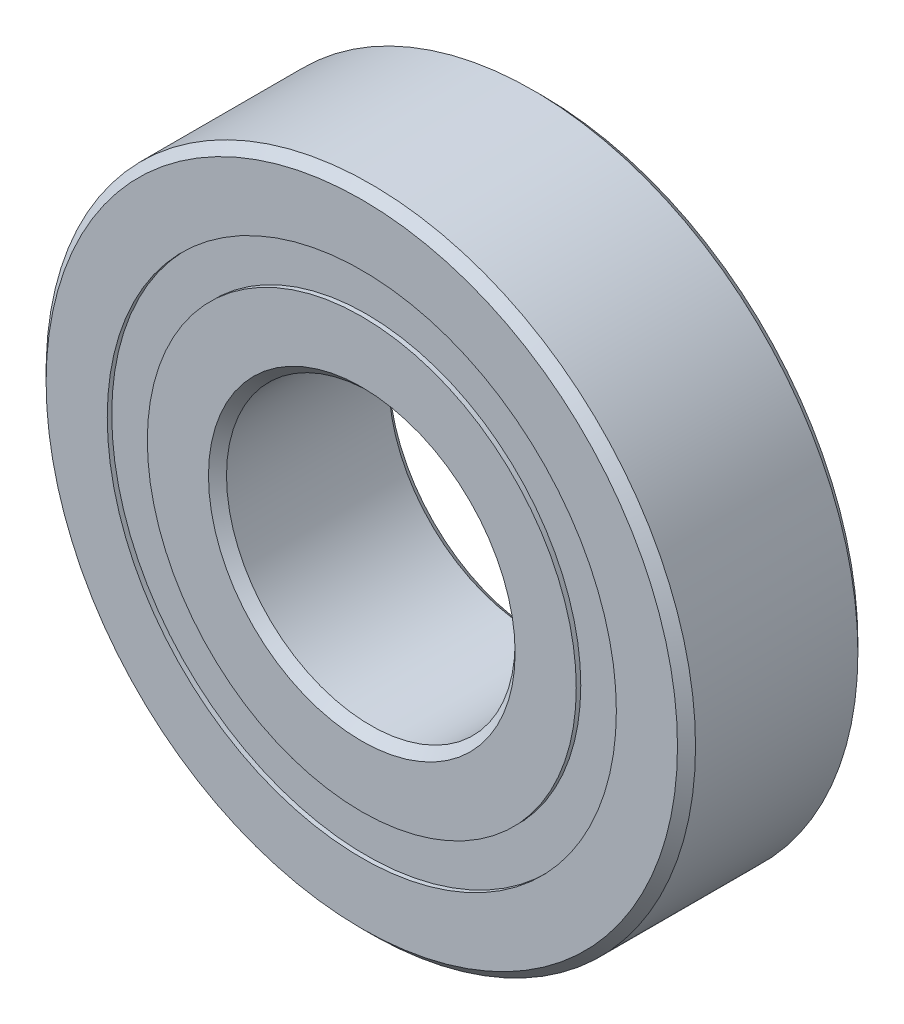
SolidWorks part; units mm, degrees
ref_plane "Front Plane" through (0, 0, 0) normal (0, 0, 1) x (1, 0, 0)
ref_plane "Top Plane" through (0, 0, 0) normal (0, 1, 0) x (1, 0, 0)
ref_plane "Right Plane" through (0, 0, 0) normal (1, 0, 0) x (0, 0, -1)
sketch "Sketch1" plane through (0, 0, 0) normal (1, 0, 0) x (0, 0, -1)
  line L0 (-1.25, 0) -> (1.25, 0) construction
  line L1 (0, 4.5) -> (0, -4.5) construction
  line L2 (1.125, 4.5) -> (-1.125, 4.5)
  line L3 (-1.125, 4.5) -> (-1.25, 4.375)
  line L4 (-1.25, 4.375) -> (-1.25, 3.5278)
  line L5 (-1.25, 3.5278) -> (-0.5556, 3.5278)
  line L6 (1.25, 3.5278) -> (0.5556, 3.5278)
  line L7 (1.25, 4.375) -> (1.25, 3.5278)
  line L8 (1.125, 4.5) -> (1.25, 4.375)
  line L9 (0, 4.5) -> (0, 3.25) construction
  line L10 (0, 3.25) -> (0, 2) construction
  arc A0 (-0.5556, 3.5278) -> (0.5556, 3.5278) centre (0, 3.25) cw
  arc A1 (-0.5556, 3.5278) -> (0.5556, 3.5278) centre (0, 3.25) ccw construction
  point P14 (0, 2)
  point P15 (0, -2)
  dimension "Width" = 2.5
  dimension "OD" = 9
  dimension "D1" = 45
  dimension "D2" = 0.125
  dimension "D3" = 1.1111
  dimension "Shaft Dia" = 4
  dimension "D4" = 0.2778
revolve "Revolve1" add sketch "Sketch1" angle 360 about L0
sketch "Sketch2" plane through (0, 0, 0) normal (1, 0, 0) x (0, 0, -1)
  line L0 (-1.25, 2.9722) -> (-0.5556, 2.9722)
  line L1 (-1.25, 4.375) -> (-1.25, -4.375) construction
  line L2 (-1.25, 2.9722) -> (-1.25, 2.125)
  line L3 (-1.25, 2.125) -> (-1.125, 2)
  line L4 (-1.125, 2) -> (1.125, 2)
  line L5 (0, 4.5) -> (0, -4.5) construction
  line L6 (0, 2) -> (0, 2.6289) construction
  line L7 (0, 2.6289) -> (0, 2) construction
  line L8 (-1.25, 2.9722) -> (-1.25, 1.2778) construction
  line L10 (1.25, 2.9722) -> (0.5556, 2.9722)
  line L11 (1.25, 2.9722) -> (1.25, 2.125)
  line L12 (1.25, 2.125) -> (1.125, 2)
  arc A0 (-0.5556, 2.9722) -> (0.5556, 2.9722) centre (0, 3.25) ccw
  arc A1 (0.5556, 3.5278) -> (-0.5556, 3.5278) centre (0, 3.25) ccw construction
  circle A2 centre (0, 3.25) radius 0.6211 construction
  dimension "D1" = 0.125
  dimension "D2" = 45
revolve "Revolve2" add sketch "Sketch2" angle 360 about L0
sketch "Sketch3" plane through (0, 0, 0) normal (1, 0, 0) x (0, 0, -1)
  line L0 (-0.6211, 3.25) -> (0.6211, 3.25)
  line L1 (0, 3.25) -> (0, 0) construction
  circle A1 centre (0, 3.25) radius 0.6211 construction
  arc A2 (-0.6211, 3.25) -> (0.6211, 3.25) centre (0, 3.25) cw
  arc A3 (0.5556, 3.5278) -> (-0.5556, 3.5278) centre (0, 3.25) ccw construction
  dimension "D1" = 1.2423
  dimension "D2" = 3.25
revolve "Revolve3" add sketch "Sketch3" angle 360 about L0
ref_axis "Axis1" through (0, 0, -1.25) along (0, 0, 1)
pattern_circular "CirPattern1" count 15 every 24 about axis through (0, 0, -1.25) along (0, 0, 1) of bodies 104
sketch "Sketch5" plane through (0, 0, 0) normal (1, 0, 0) x (0, 0, -1)
  line L0 (-1.25, 2.9722) -> (-0.5556, 2.9722) construction
  line L1 (-1.1875, 3.5278) -> (-0.6211, 3.5278)
  line L2 (-1.1875, 3.5278) -> (-1.1875, 2.9722)
  line L3 (-1.1875, 2.9722) -> (-0.6211, 2.9722)
  line L4 (-0.6211, 3.5278) -> (-0.6211, 2.9722)
  line L5 (0.6211, 3.5278) -> (1.1875, 3.5278)
  line L6 (0.6211, 3.5278) -> (0.6211, 2.9722)
  line L7 (0.6211, 2.9722) -> (1.1875, 2.9722)
  line L8 (1.1875, 3.5278) -> (1.1875, 2.9722)
  line L9 (-1.25, 3.5278) -> (-0.5556, 3.5278) construction
  line L10 (-1.1875, 4.4375) -> (-1.1875, 3.5278) construction
  line L11 (-1.125, 4.5) -> (-1.25, 4.375) construction
  circle A0 centre (0, 3.25) radius 0.6211 construction
revolve "Revolve5" add sketch "Sketch5" angle 360 about L0
sketch "Sketch6" plane through (0, 0, 0) normal (0, 1, 0) x (1, 0, 0)
  point P0 (4.5, -1.25)
  point P1 (4.5, 1.25)
  dimension "D1" = 2.5
ref_axis "Center Axis 1" through (0, 0, -2.2011) along (0, 0, 1)
ref_plane "Contact Plane 1" through (0, 0, 1.25) normal (0, 0, 1) x (1, 0, 0)
ref_plane "Contact Plane 2" through (0, 0, -1.25) normal (0, 0, -1) x (-1, 0, 0)
equation "\"D2@Sketch1\" = \"Width@Sketch1\"*.05"
equation "\"D3@Sketch1\" = \"Width@Sketch1\"/2.25"
equation "\"D4@Sketch1\" = \"D3@Sketch1\"/4"
equation "\"Balls@CirPattern1\"=\"D2@Sketch3\"*2*pi/\"D1@Sketch3\"-1"
equation "\"D2@CirPattern1\" = 360/\"Balls@CirPattern1\""
equation "\"D1@Sketch2\"=\"D2@Sketch1\""
equation "\"D1@Sketch6\"=\"Width@Sketch1\""
